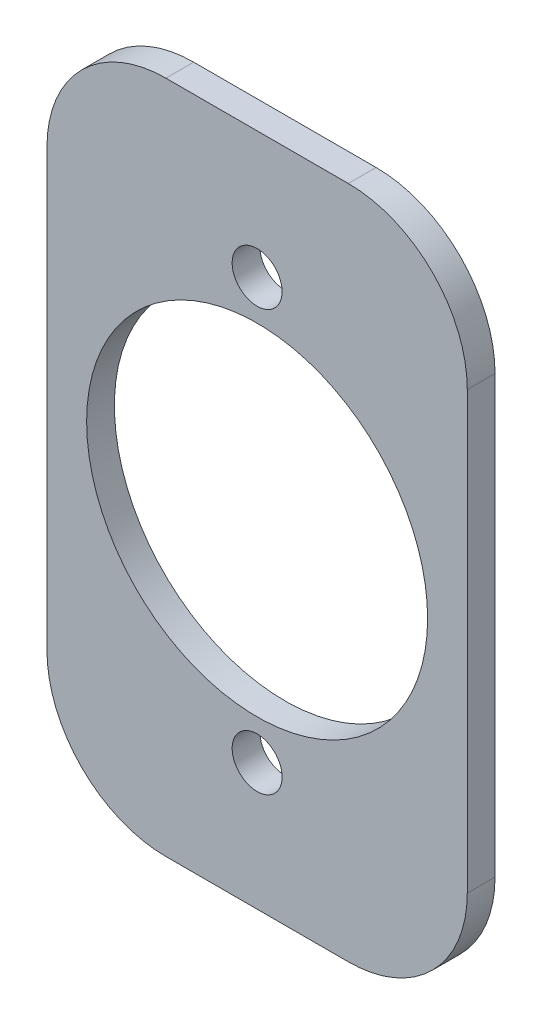
SolidWorks part; units mm, degrees
ref_plane "Front Plane" through (0, 0, 0) normal (0, 0, 1) x (1, 0, 0)
ref_plane "Top Plane" through (0, 0, 0) normal (0, 1, 0) x (1, 0, 0)
ref_plane "Right Plane" through (0, 0, 0) normal (1, 0, 0) x (0, 0, -1)
sketch "Sketch1" plane through (0, 0, 0) normal (0, 0, 1) x (1, 0, 0)
  line L5 (25, 65) -> (-25, 65)
  line L6 (33, 57) -> (33, -57)
  line L7 (25, -65) -> (-25, -65)
  line L8 (-33, 57) -> (-33, -57)
  line L9 (33, 65) -> (-33, -65) construction
  line L10 (33, -65) -> (-33, 65) construction
  arc A4 (-33, -57) -> (-25, -65) centre (-25, -57) ccw
  arc A5 (25, -65) -> (33, -57) centre (25, -57) ccw
  arc A6 (33, 57) -> (25, 65) centre (25, 57) ccw
  arc A7 (-33, 57) -> (-25, 65) centre (-25, 57) cw
  point P0 (0, 0)
  dimension "D1" = 130
  dimension "D2" = 8
  dimension "D3" = 50
extrude "Boss-Extrude1" add sketch "Sketch1" along normal blind 5
sketch "Sketch4" plane through (0, 0, 0) normal (0, 0, -1) x (-1, 0, 0)
  line L1 (-26.5, -42.5) -> (26.5, -42.5)
  line L2 (-26.5, -42.5) -> (-26.5, 42.5)
  line L3 (-26.5, 42.5) -> (26.5, 42.5)
  line L4 (26.5, -42.5) -> (26.5, 42.5)
  line L5 (-26.5, -42.5) -> (26.5, 42.5) construction
  line L6 (-26.5, 42.5) -> (26.5, -42.5) construction
  point P0 (0, 0)
  dimension "D1" = 85
  dimension "D2" = 53
extrude "Boss-Extrude2" add sketch "Sketch4" along normal blind 3.5
sketch "Sketch2" plane through (0, 0, 5) normal (0, 0, 1) x (1, 0, 0)
  circle A0 centre (0, 0) radius 21.5
  dimension "D1" = 43
extrude "Cut-Extrude1" cut sketch "Sketch2" against normal through all
sketch "Sketch3" plane through (0, 0, 5) normal (0, 0, 1) x (1, 0, 0)
  line L0 (0, 26.5) -> (0, -26.5) construction
  circle A0 centre (0, 26.5) radius 3.15
  circle A1 centre (0, -26.5) radius 3.15
  point P3 (0, 0)
  dimension "D2" = 6.3
  dimension "D1" = 53
extrude "Cut-Extrude2" cut sketch "Sketch3" against normal through all
sketch "Sketch16" plane through (0, 0, 0) normal (0, 0, -1) x (-1, 0, 0)
  line L1 (-26.5, 42.5) -> (26.5, 42.5)
  line L2 (-26.5, 42.5) -> (-26.5, -42.5)
  line L3 (-26.5, -42.5) -> (26.5, -42.5)
  line L4 (26.5, 42.5) -> (26.5, -42.5)
  line L5 (-40.0582, 69.876) -> (42.0159, 69.876)
  line L6 (-40.0582, 69.876) -> (-40.0582, -70.1772)
  line L7 (-40.0582, -70.1772) -> (42.0159, -70.1772)
  line L8 (42.0159, 69.876) -> (42.0159, -70.1772)
extrude "lazy cut" cut sketch "Sketch16" against normal through all
fillet "Fillet1" radius 15 4 edges at (-26.5, -42.5, 0.75) (26.5, -42.5, 0.75) (26.5, 42.5, 0.75) (-26.5, 42.5, 0.75)
sketch "Sketch17" plane through (0, 42.5, 0) normal (0, 1, 0) x (1, 0, 0)
  line L0 (26.5, 3.5) -> (26.5, -5) construction
  line L1 (-26.5, -5) -> (26.5, -5)
  line L2 (-26.5, -5) -> (-26.5, 0)
  line L3 (-26.5, 0) -> (26.5, 0)
  line L4 (26.5, -5) -> (26.5, 0)
  line L5 (26.5, 3.5) -> (11.5, 3.5) construction
  dimension "D1" = 3.5
extrude "Cut-Extrude7" cut sketch "Sketch17" against normal through all
sketch "Sketch12" plane through (0, 0, 5) normal (0, 0, 1) x (1, 0, 0)
  line L6 (0, 0) -> (0, 59.75) construction
  line L7 (0, 59.75) -> (-27.75, 59.75) construction
  line L8 (0, 0) -> (-27.75, 0) construction
  line L9 (-27.75, 0) -> (-27.75, 59.75) construction
  line L10 (-27.75, 59.75) -> (-30.6569, 59.446) construction
  circle A0 centre (-27.75, 59.75) radius 2.9
  circle A1 centre (27.75, 59.75) radius 2.9
  circle A2 centre (-27.75, -59.75) radius 2.9
  circle A3 centre (27.75, -59.75) radius 2.9
  circle A4 centre (-27.75, 59.75) radius 3 construction
  dimension "D3" = 5.8
  dimension "D4" = 6
  dimension "D1" = 27.75
  dimension "D2" = 59.75
extrude "Cut-Extrude3" [suppressed] cut sketch "Sketch12" against normal blind 3
sketch "Sketch13" [suppressed] plane through (0, 0, 2) normal (0, 0, 1) x (1, 0, 0)
  line L0 (0, 0) -> (0, 65) construction
  line L1 (25, 65) -> (-25, 65) construction
  line L2 (0, 0) -> (-27.75, 0) construction
  circle A0 centre (-27.75, 59.75) radius 1.75
  circle A1 centre (27.75, 59.75) radius 1.75
  circle A2 centre (27.75, -59.75) radius 1.75
  circle A3 centre (-27.75, -59.75) radius 1.75
  dimension "D1" = 3.5
extrude "Cut-Extrude4" [suppressed] cut sketch "Sketch13" against normal through all
sketch "Sketch14" plane through (0, 0, 5) normal (0, 0, 1) x (1, 0, 0)
  line L0 (5.5, 0) -> (-5.5, 0) construction
  line L1 (-5.5, 26.5) -> (-5.5, -26.5)
  line L3 (5.5, 26.5) -> (5.5, -26.5)
  line L4 (-5.5, -26.5) -> (-3.65, -26.5) construction
  arc A2 (5.5, 26.5) -> (-5.5, 26.5) centre (0, 26.5) ccw
  arc A3 (-5.5, 26.5) -> (5.5, 26.5) centre (0, 26.5) ccw construction
  arc A4 (-5.5, -26.5) -> (5.5, -26.5) centre (0, -26.5) cw construction
  arc A5 (5.5, -26.5) -> (-5.5, -26.5) centre (0, -26.5) cw
  point P7 (0, 0)
  dimension "D2" = 11
extrude "Cut-Extrude5" [suppressed] cut sketch "Sketch14" against normal blind 3 contours L3 A5 L1 A2
sketch "Sketch15" [suppressed] plane through (0, 0, 5) normal (0, 0, 1) x (1, 0, 0)
  line L1 (-2.5, 65) -> (-2.5, 31.399)
  line L2 (25, 65) -> (-25, 65) construction
  line L3 (0, 0) -> (-33, 0) construction
  line L4 (-33, 57) -> (-33, -57) construction
  line L5 (0, 65) -> (0, 0) construction
  line L6 (-27.75, 13.75) -> (-20.8791, 13.75)
  line L7 (-2.5, 65) -> (2.5, 65)
  line L8 (-21.75, 59.75) -> (-6.75, 59.75)
  line L9 (-27.75, 53.75) -> (-27.75, 13.75)
  line L10 (-6.75, 59.75) -> (-6.75, 24.0715)
  line L11 (2.5, 65) -> (2.5, 31.399)
  line L12 (27.75, 13.75) -> (20.8791, 13.75)
  line L13 (6.75, 59.75) -> (6.75, 24.0715)
  line L14 (21.75, 59.75) -> (6.75, 59.75)
  line L15 (27.75, 53.75) -> (27.75, 13.75)
  line L16 (27.75, -53.75) -> (27.75, -13.75)
  line L17 (21.75, -59.75) -> (6.75, -59.75)
  line L18 (6.75, -59.75) -> (6.75, -24.0715)
  line L19 (27.75, -13.75) -> (20.8791, -13.75)
  line L20 (2.5, -65) -> (2.5, -31.399)
  line L21 (-6.75, -59.75) -> (-6.75, -24.0715)
  line L22 (-27.75, -53.75) -> (-27.75, -13.75)
  line L23 (-21.75, -59.75) -> (-6.75, -59.75)
  line L24 (-2.5, -65) -> (2.5, -65)
  line L25 (-27.75, -13.75) -> (-20.8791, -13.75)
  line L26 (-2.5, -65) -> (-2.5, -31.399)
  arc A3 (-6.75, 24.0715) -> (-20.8791, 13.75) centre (0, 0) ccw
  arc A4 (-27.75, 53.75) -> (-21.75, 59.75) centre (-27.75, 59.75) ccw
  arc A5 (2.5, 31.399) -> (-2.5, 31.399) centre (0, 26.5) ccw
  arc A6 (6.75, 24.0715) -> (20.8791, 13.75) centre (0, 0) cw
  arc A7 (27.75, 53.75) -> (21.75, 59.75) centre (27.75, 59.75) cw
  arc A8 (-21.75, -59.75) -> (-27.75, -53.75) centre (-27.75, -59.75) cw construction
  arc A9 (27.75, -53.75) -> (21.75, -59.75) centre (27.75, -59.75) ccw
  arc A10 (6.75, -24.0715) -> (20.8791, -13.75) centre (0, 0) ccw
  arc A11 (-21.75, 59.75) -> (-27.75, 53.75) centre (-27.75, 59.75) ccw construction
  arc A12 (2.5, -31.399) -> (-2.5, -31.399) centre (0, -26.5) cw
  arc A13 (-27.75, -53.75) -> (-21.75, -59.75) centre (-27.75, -59.75) cw
  arc A14 (-6.75, -24.0715) -> (-20.8791, -13.75) centre (0, 0) cw
  dimension "D1" = 50
  dimension "D2" = 15
  dimension "D4" = 12
  dimension "D3" = 2.5
  dimension "D5" = 40
extrude "Cut-Extrude6" [suppressed] cut sketch "Sketch15" against normal blind 1.5
